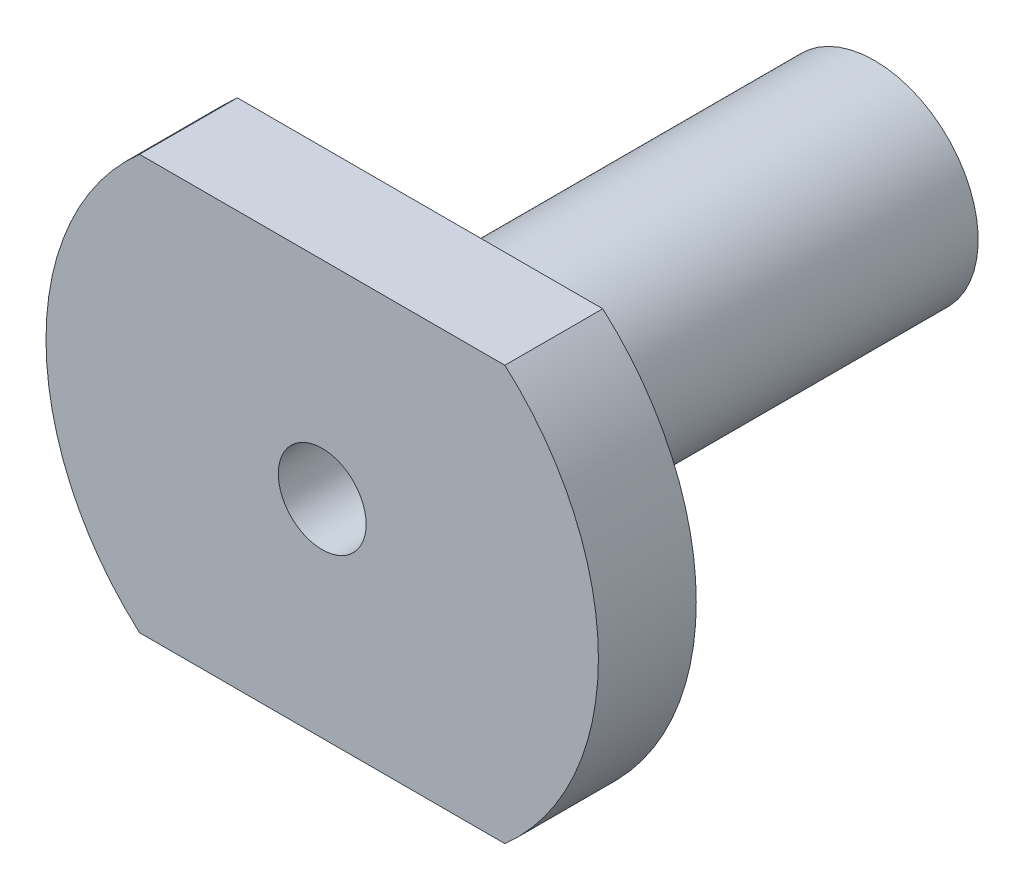
SolidWorks part; units mm, degrees
material "Alloy Steel"
ref_plane "Front Plane" through (0, 0, 0) normal (0, 0, 1) x (1, 0, 0)
ref_plane "Top Plane" through (0, 0, 0) normal (0, 1, 0) x (1, 0, 0)
ref_plane "Right Plane" through (0, 0, 0) normal (1, 0, 0) x (0, 0, -1)
sketch "Sketch1" plane through (0, 0, 0) normal (1, 0, 0) x (0, 0, -1)
  line L0 (0, 0) -> (-45857.0772, 0) construction
  line L1 (0, 0) -> (0, 12.7)
  line L2 (0, 12.7) -> (4.5, 12.7)
  line L3 (4.5, 12.7) -> (4.5, 6.0325)
  line L4 (5.77, 4.7625) -> (25.4, 4.7625)
  line L5 (25.4, 4.7625) -> (25.4, 0)
  line L6 (7.2136, 4.7625) -> (7.2136, 27.6611) construction
  line L7 (7.2136, 27.6611) -> (21.1836, 27.6611) construction
  line L8 (21.1836, 27.6611) -> (21.1836, 4.7625) construction
  line L10 (5.77, 4.7625) -> (5.77, 9.4131) construction
  line L11 (24.82, 9.4131) -> (15.295, 9.4131) construction
  line L12 (15.295, 9.4131) -> (5.77, 9.4131) construction
  line L13 (24.82, 9.4131) -> (24.82, 4.7625) construction
  line L14 (15.295, 9.4131) -> (15.295, 4.7625) construction
  line L15 (0, 0) -> (25.4, 0)
  line L16 (5.77, 4.7625) -> (5.77, 6.0325)
  line L17 (5.77, 6.0325) -> (4.5, 6.0325)
  point P6 (4.5, 4.7625)
  dimension "D1" = 12.7
  dimension "D2" = 21.1836
  dimension "D3" = 13.97
  dimension "D5" = 1.27
  dimension "D4" = 4.5
  dimension "D6" = 1.27
  dimension "D7" = 4.7625
  dimension "D8" = 9.525
  dimension "D9" = 25.4
revolve "Revolve1" add sketch "Sketch1" angle 360 about L15
hole_wizard "Tap Drill for #10-32 Tap1" positions "Sketch2" profile "Sketch4" hole size "#10-32" standard "ANSI Inch" end condition through all
sketch "Sketch2" plane through (0, 0, 0) normal (0, 0, 1) x (1, 0, 0)
  point P0 (0, 0)
sketch "Sketch4" plane through (0, 0, 0) normal (1, 0, 0) x (0, -1, 0)
  line L0 (0, 0) -> (0, 25.4)
  line L1 (0, 25.4) -> (2.0193, 25.4)
  line L2 (2.0193, 25.4) -> (2.0193, 0)
  line L5 (2.0193, 0) -> (0, 0)
  line L11 (0, -6.35) -> (0, 107.95) construction
  dimension "Thru Hole Dia." = 4.0386
  dimension "Thru Hole Depth" = 25.4
sketch "Sketch5" plane through (0, 0, 0) normal (0, 0, 1) x (1, 0, 0)
  line L1 (12.7, -9.525) -> (-12.7, -9.525)
  line L2 (12.7, -9.525) -> (12.7, 9.525) construction
  line L3 (12.7, 9.525) -> (-12.7, 9.525)
  line L4 (-12.7, -9.525) -> (-12.7, 9.525) construction
  line L5 (12.7, -9.525) -> (-12.7, 9.525) construction
  line L6 (12.7, 9.525) -> (-12.7, -9.525) construction
  line L7 (-12.7, 9.525) -> (12.7, 9.525)
  line L8 (-12.7, 9.525) -> (-12.7, 12.7)
  line L9 (-12.7, 12.7) -> (12.7, 12.7)
  line L10 (12.7, 9.525) -> (12.7, 12.7)
  line L11 (-12.7, -9.525) -> (12.7, -9.525)
  line L12 (-12.7, -9.525) -> (-12.7, -12.7)
  line L13 (-12.7, -12.7) -> (12.7, -12.7)
  line L14 (12.7, -9.525) -> (12.7, -12.7)
  circle A0 centre (0, 0) radius 12.7 construction
  point P0 (0, 0)
  dimension "D1" = 19.05
extrude "Cut-Extrude1" cut sketch "Sketch5" against normal through all contours L12 L13 L14 L11 | L8 L9 L10 L7
